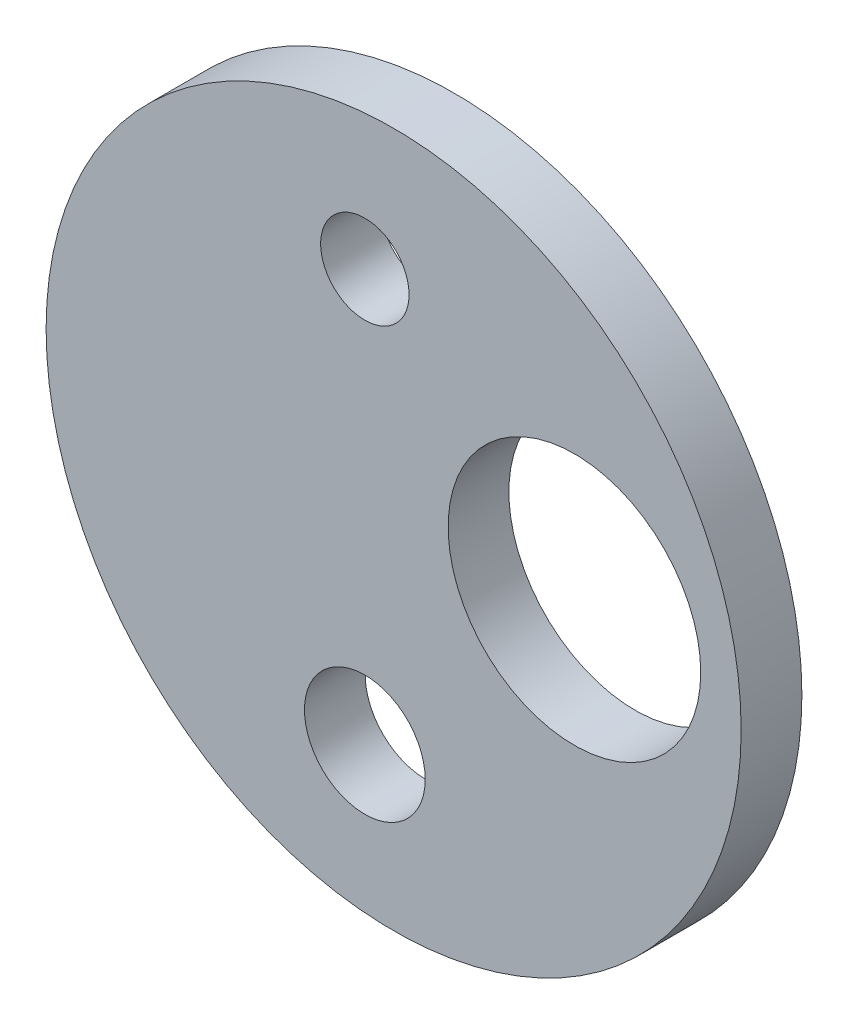
SolidWorks part; units mm, degrees
ref_plane "Alzado" through (0, 0, 0) normal (0, 0, 1) x (1, 0, 0)
ref_plane "Planta" through (0, 0, 0) normal (0, 1, 0) x (1, 0, 0)
ref_plane "Vista lateral" through (0, 0, 0) normal (1, 0, 0) x (0, 0, -1)
sketch "Croquis1" plane through (0, 0, 0) normal (0, 0, 1) x (1, 0, 0)
  circle A0 centre (0, 0) radius 57.2267
  circle A1 centre (-4.742, 34.7594) radius 7.278
  circle A2 centre (-4.742, -33.0459) radius 9.9402
  circle A3 centre (29.7726, 4.8957) radius 20.7966
  point P9 (29.7726, 4.8957)
extrude "Saliente-Extruir1" add sketch "Croquis1" along normal blind 10
